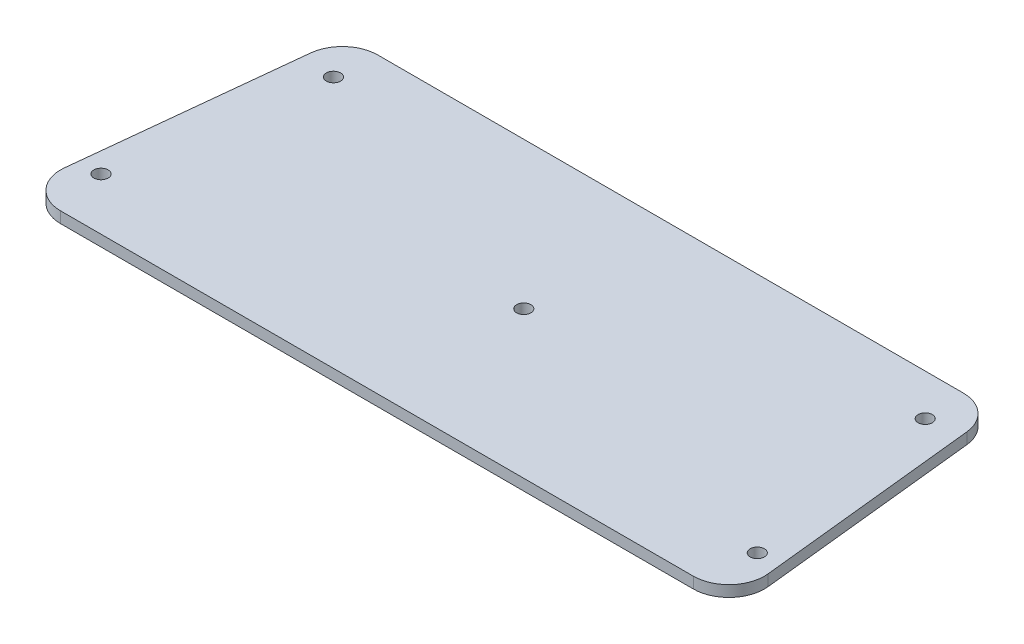
SolidWorks part; units mm, degrees
ref_plane "Front Plane" through (0, 0, 0) normal (0, 0, 1) x (1, 0, 0)
ref_plane "Top Plane" through (0, 0, 0) normal (0, 1, 0) x (1, 0, 0)
ref_plane "Right Plane" through (0, 0, 0) normal (1, 0, 0) x (0, 0, -1)
sketch "Sketch1" plane through (0, 0, 0) normal (0, 1, 0) x (1, 0, 0)
  line L0 (-101.6, -41.91) -> (-92.71, 41.91)
  line L1 (-101.6, -41.91) -> (101.6, -41.91)
  line L2 (-101.6, -41.91) -> (-101.6, 41.91)
  line L3 (-101.6, 41.91) -> (101.6, 41.91)
  line L4 (101.6, -41.91) -> (101.6, 41.91)
  line L5 (-101.6, -41.91) -> (101.6, 41.91) construction
  line L6 (-101.6, 41.91) -> (101.6, -41.91) construction
  line L7 (0, 41.91) -> (0, -41.91) construction
  line L8 (101.6, -41.91) -> (92.71, 41.91)
  circle A0 centre (0, 0) radius 2.032
  circle A1 centre (-93.6752, -27.0205) radius 2.032
  circle A2 centre (-84.4677, 30.1295) radius 2.032
  circle A3 centre (93.6752, -27.0205) radius 2.032
  circle A4 centre (84.4677, 30.1295) radius 2.032
  point P0 (0, 0)
  point P19 (0, 0)
  dimension "D1" = 4.064
  dimension "D6" = 4.064
  dimension "D2" = 203.2
  dimension "D3" = 83.82
  dimension "D4" = 8.89
  dimension "D5" = 83.946
  dimension "D7" = 14.8895
  dimension "D8" = 7.9248
  dimension "D9" = 57.15
  dimension "D10" = 9.2075
extrude "Boss-Extrude1" add sketch "Sketch1" along normal blind 3.175 contours L1 L8 L3 L0 A3 A2 A1 A0 A4 region at (-94.9692, 0, 0.2318)
fillet "Fillet1" radius 10.16 2 edges at (101.6, 1.5875, 41.91) (-101.6, 1.5875, 41.91)
fillet "Fillet2" radius 10.16 2 edges at (-92.71, 1.5875, -41.91) (92.71, 1.5875, -41.91)
